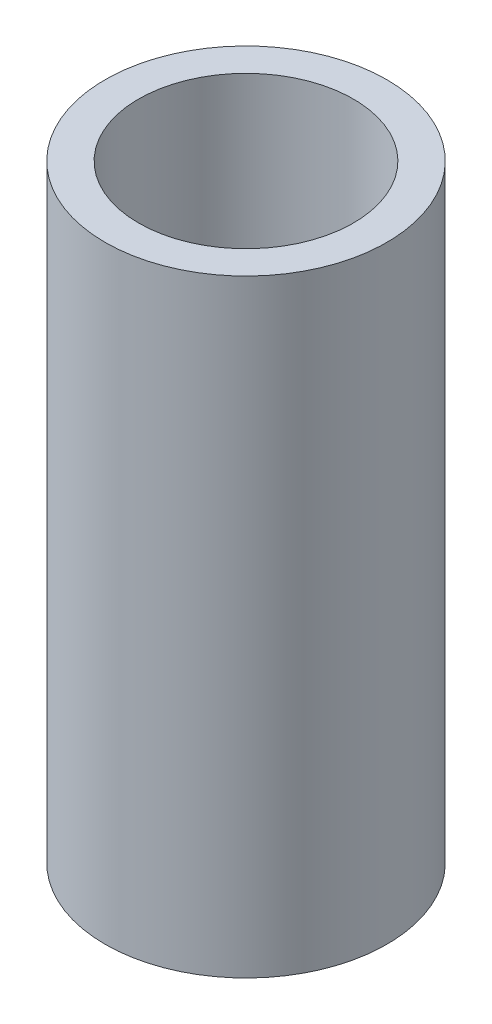
SolidWorks part; units mm, degrees
ref_plane "Front Plane" through (0, 0, 0) normal (0, 0, 1) x (1, 0, 0)
ref_plane "Top Plane" through (0, 0, 0) normal (0, 1, 0) x (1, 0, 0)
ref_plane "Right Plane" through (0, 0, 0) normal (1, 0, 0) x (0, 0, -1)
sketch "Sketch1" plane through (0, 0, 0) normal (0, 1, 0) x (1, 0, 0)
  circle A0 centre (0, 0) radius 32.5
  dimension "SLEEVE_OD" = 65
extrude "Boss-Extrude1" add sketch "Sketch1" along normal blind 140.2091
sketch "Sketch2" plane through (0, 0, 0) normal (0, 1, 0) x (1, 0, 0)
  circle A0 centre (0, 0) radius 24.7783
  dimension "BORE_D" = 49.5567
extrude "Cut-Extrude1" cut sketch "Sketch2" along normal through all
chamfer "Chamfer1" distance 3.9542 angle 60 rebuild error yes
